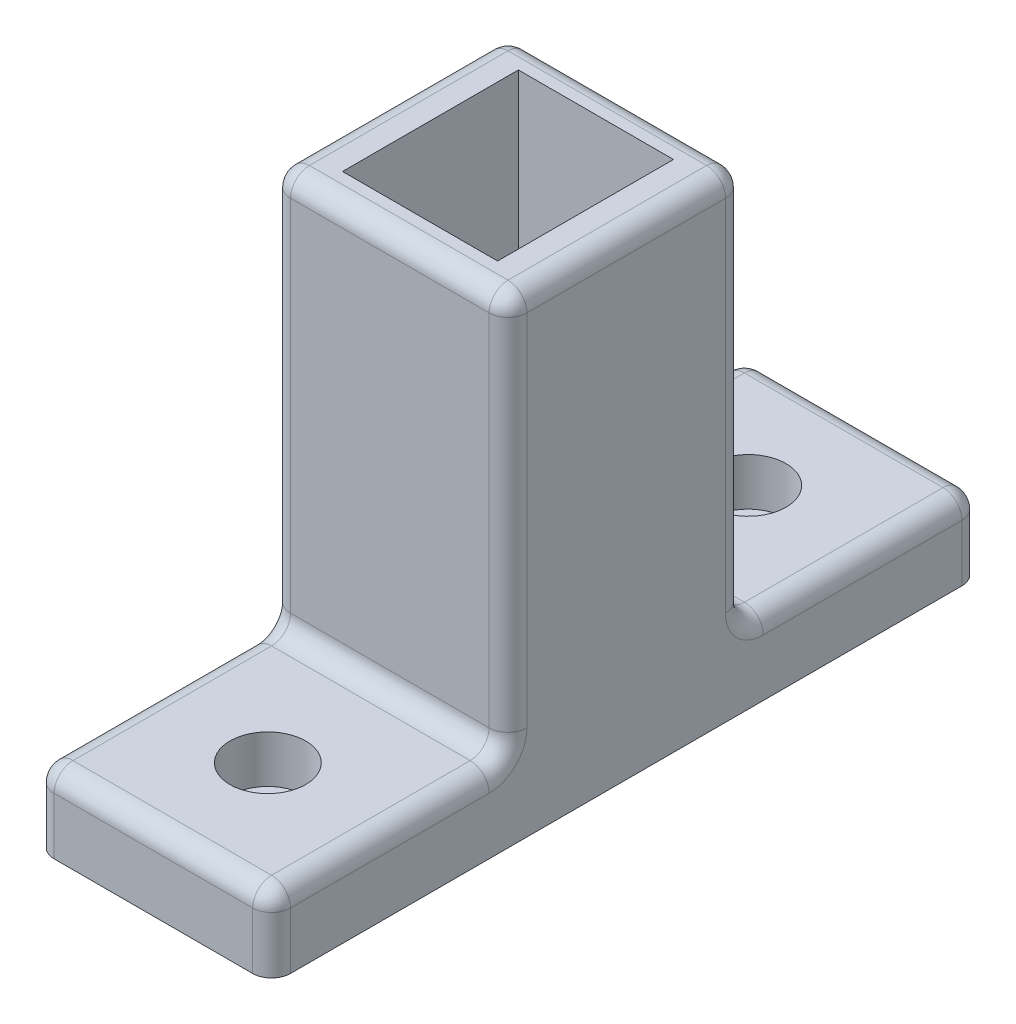
SolidWorks part; units mm, degrees
material "ABS"
ref_plane "Front Plane" through (0, 0, 0) normal (0, 0, 1) x (1, 0, 0)
ref_plane "Top Plane" through (0, 0, 0) normal (0, 1, 0) x (1, 0, 0)
ref_plane "Right Plane" through (0, 0, 0) normal (1, 0, 0) x (0, 0, -1)
sketch "Sketch1" plane through (0, 0, 0) normal (0, 1, 0) x (1, 0, 0)
  line L1 (-8.2, -9.3) -> (8.2, -9.3)
  line L2 (-8.2, -9.3) -> (-8.2, 9.3)
  line L3 (-8.2, 9.3) -> (8.2, 9.3)
  line L4 (8.2, -9.3) -> (8.2, 9.3)
  line L5 (-8.2, -9.3) -> (8.2, 9.3) construction
  line L6 (-8.2, 9.3) -> (8.2, -9.3) construction
  line L7 (-12.5, -12.5) -> (12.5, -12.5)
  line L8 (-12.5, -12.5) -> (-12.5, 12.5)
  line L9 (-12.5, 12.5) -> (12.5, 12.5)
  line L10 (12.5, -12.5) -> (12.5, 12.5)
  line L11 (-12.5, -12.5) -> (12.5, 12.5) construction
  line L12 (-12.5, 12.5) -> (12.5, -12.5) construction
  point P0 (0, 0)
  point P6 (0, 0)
  dimension "D1" = 16.4
  dimension "D2" = 18.6
  dimension "D3" = 25
  dimension "D4" = 25
extrude "Boss-Extrude1" add sketch "Sketch1" along normal blind 50
sketch "Sketch6" plane through (0, 0, 0) normal (0, 1, 0) x (1, 0, 0)
  line L13 (-12.5, -37.5) -> (12.5, -37.5)
  line L14 (-12.5, -37.5) -> (-12.5, 37.5)
  line L15 (-12.5, 37.5) -> (12.5, 37.5)
  line L16 (12.5, -37.5) -> (12.5, 37.5)
  line L17 (-12.5, -37.5) -> (12.5, 37.5) construction
  line L18 (-12.5, 37.5) -> (12.5, -37.5) construction
  point P4 (0, 0)
  dimension "D5" = 75
  dimension "D6" = 25
extrude "Boss-Extrude3" add sketch "Sketch6" along normal blind 8
fillet "Fillet2" radius 2 20 edges at (0, 8, -12.5) (0, 50, -12.5) (12.5, 29, -12.5) (12.5, 50, 0) (12.5, 29, 12.5) (-12.5, 29, 12.5) (0, 50, 12.5) (-12.5, 29, -12.5) (-12.5, 50, 0) (-12.5, 8, -25) (12.5, 8, -25) (0, 8, -37.5) (0, 8, 37.5) (-12.5, 8, 25) (0, 8, 12.5) (12.5, 8, 25) (12.5, 4, -37.5) (-12.5, 4, -37.5) (12.5, 4, 37.5) (-12.5, 4, 37.5)
sketch "Sketch7" plane through (0, 8, 0) normal (0, 1, 0) x (1, 0, 0)
  line L0 (0, 0) -> (0, 25.4) construction
  line L1 (0, 0) -> (0, -25.4) construction
  circle A0 centre (0, 0) radius 4
  circle A1 centre (0, 25.4) radius 4
  circle A2 centre (0, -25.4) radius 4
extrude "Cut-Extrude1" cut sketch "Sketch7" against normal blind 5
sketch "Sketch8" plane through (0, 0, 0) normal (0, 1, 0) x (1, 0, 0)
  line L0 (0, 0) -> (0, 25.4) construction
  line L1 (0, 0) -> (0, -25.4) construction
  circle A0 centre (0, 0) radius 2.3813
  circle A1 centre (0, 25.4) radius 2.3813
  circle A2 centre (0, -25.4) radius 2.3813
extrude "Cut-Extrude4" cut sketch "Sketch8" against normal through all and the other way through all
